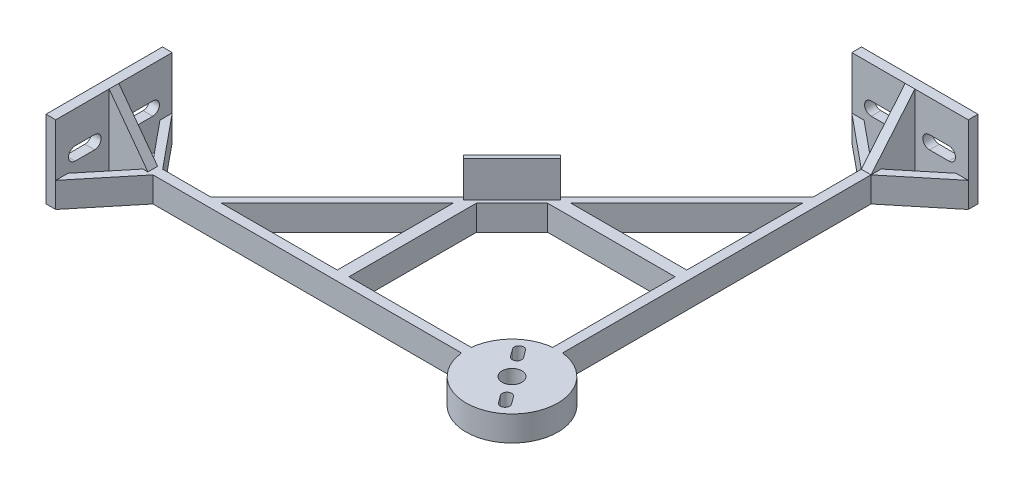
SolidWorks part; units mm, degrees
material "ABS"
ref_plane "Front Plane" through (0, 0, 0) normal (0, 0, 1) x (1, 0, 0)
ref_plane "Top Plane" through (0, 0, 0) normal (0, 1, 0) x (1, 0, 0)
ref_plane "Right Plane" through (0, 0, 0) normal (1, 0, 0) x (0, 0, -1)
sketch "Sketch1" plane through (0, 0, 0) normal (0, 1, 0) x (1, 0, 0)
  line L0 (-1.5875, 14.9158) -> (-1.5875, 130.175)
  line L1 (1.5875, 130.175) -> (1.5875, 14.9158)
  line L2 (-1.5875, 130.175) -> (1.5875, 130.175)
  line L4 (-14.9158, -1.5875) -> (-130.175, -1.5875)
  line L5 (-130.175, -1.5875) -> (-130.175, 1.5875)
  line L8 (-130.175, 1.5875) -> (-14.9158, 1.5875)
  line L9 (0, 0) -> (-130.175, 0) construction
  line L11 (0, 0) -> (0, 146.05) construction
  circle A0 centre (0, 0) radius 15
  point P19 (0, 0)
  point P21 (0, 0)
  dimension "D1" = 30
  dimension "D2" = 3.175
  dimension "D4" = 1.5875
  dimension "D3" = 2
  dimension "D5" = 130.175
extrude "Boss-Extrude2" add sketch "Sketch1" along normal blind 8.255 contours A0
extrude "Boss-Extrude3" add sketch "Sketch1<6>" along normal blind 8.255 contours L4 A0 | A0 | A0 region at (0, 0, -72.5735) region at (-72.5735, 0, 0)
sketch "Sketch1<6>" plane through (0, 0, 0) normal (0, 1, 0) x (1, 0, 0) same geometry as "Sketch1"
sketch "Sketch5" plane through (0, 8.255, 0) normal (0, 1, 0) x (1, 0, 0)
  line L0 (0, 0) -> (130.175, 0) construction
  line L1 (0, 0) -> (0, -22.3627) construction
  line L2 (-6.4967, 8.7797) -> (0, 0) construction
  line L3 (-4.6836, 6.3296) -> (-6.4967, 8.7797) construction
  line L4 (-5.9087, 5.4231) -> (-7.7217, 7.8732)
  line L5 (-3.4586, 7.2361) -> (-5.2716, 9.6862)
  line L6 (0, 0) -> (1.0099, 0.7473) construction
  line L7 (4.6836, -6.3296) -> (6.4967, -8.7797) construction
  line L8 (3.4586, -7.2361) -> (5.2716, -9.6862)
  line L9 (5.9087, -5.4231) -> (7.7217, -7.8732)
  line L10 (-1.5875, 130.175) -> (1.5875, 130.175) construction
  arc A0 (3.4586, -7.2361) -> (5.9087, -5.4231) centre (4.6836, -6.3296) cw
  arc A1 (-5.9087, 5.4231) -> (-3.4586, 7.2361) centre (-4.6836, 6.3296) ccw
  arc A2 (-5.2716, 9.6862) -> (-7.7217, 7.8732) centre (-6.4967, 8.7797) ccw
  arc A3 (7.7217, -7.8732) -> (5.2716, -9.6862) centre (6.4967, -8.7797) cw
  circle A6 centre (0, 0) radius 3.25
  point P8 (-5.5901, 7.5546)
  point P17 (5.5901, -7.5546)
  point P18 (0, 0)
  dimension "D3" = 3.048
  dimension "D1" = 7.874
  dimension "D2" = 3.048
  dimension "D4" = 53.5
extrude "Cut-Extrude3" cut sketch "Sketch5" against normal blind 63.5
ref_axis "Axis1" through (0, 0, 0) along (0, 1, 0)
ref_plane "Plane1" through (0, 0, 0) normal (0, 0, 1) x (1, 0, 0)
ref_plane "Plane2" through (0, 0, 0) normal (1, 0, 0) x (0, 0, -1)
sketch "Sketch7" plane through (0, 0, 0) normal (1, 0, 0) x (0, 0, -1)
  line L1 (130.175, 0) -> (133.35, 0)
  line L2 (130.175, 0) -> (130.175, 25.4)
  line L3 (130.175, 25.4) -> (133.35, 25.4)
  line L4 (133.35, 0) -> (133.35, 25.4)
  dimension "D1" = 3.175
  dimension "D2" = 25.4
extrude "Boss-Extrude5" add sketch "Sketch7" along normal blind 19.05 and the other way blind 19.05
sketch "Sketch8" plane through (-19.05, 0, 0) normal (-1, 0, 0) x (0, 0, 1)
  line L1 (-133.35, 0) -> (-130.175, 0)
  line L2 (-133.35, 0) -> (-133.35, 25.4)
  line L3 (-133.35, 25.4) -> (-130.175, 25.4)
  line L4 (-130.175, 0) -> (-130.175, 25.4)
sketch "Sketch12" plane through (0, 0, -133.35) normal (0, 0, -1) x (-1, 0, 0)
  line L0 (-19.05, 12.7) -> (19.05, 12.7) construction
  line L1 (-19.05, 0) -> (-19.05, 25.4) construction
  line L2 (19.05, 0) -> (19.05, 25.4) construction
  line L3 (-6.35, 12.7) -> (-12.7, 12.7) construction
  line L4 (-6.35, 10.541) -> (-12.7, 10.541)
  line L5 (-6.35, 14.859) -> (-12.7, 14.859)
  line L6 (6.35, 12.7) -> (12.7, 12.7) construction
  line L7 (6.35, 14.859) -> (12.7, 14.859)
  line L8 (6.35, 10.541) -> (12.7, 10.541)
  line L9 (0, 12.7) -> (0, 25.4) construction
  line L10 (19.05, 25.4) -> (-19.05, 25.4) construction
  arc A0 (-6.35, 10.541) -> (-6.35, 14.859) centre (-6.35, 12.7) ccw
  arc A1 (-12.7, 14.859) -> (-12.7, 10.541) centre (-12.7, 12.7) ccw
  arc A2 (6.35, 14.859) -> (6.35, 10.541) centre (6.35, 12.7) ccw
  arc A3 (12.7, 10.541) -> (12.7, 14.859) centre (12.7, 12.7) ccw
  point P8 (-9.525, 12.7)
  point P13 (9.525, 12.7)
  dimension "D1" = 6.35
  dimension "D2" = 4.318
  dimension "D3" = 4.318
  dimension "D4" = 6.35
  dimension "D5" = 9.525
  dimension "D6" = 9.525
extrude "Cut-Extrude6" cut sketch "Sketch12" against normal through all
pattern_circular "CirPattern2" count 2 every 90 about axis through (0, 0, 0) along (0, 1, 0) of "Boss-Extrude5"
pattern_circular "CirPattern3" count 2 every 90 about axis through (0, 0, 0) along (0, 1, 0) of "Cut-Extrude6"
sketch "Sketch13" plane through (0, 0, 0) normal (0, -1, 0) x (1, 0, 0)
  line L0 (-96.6289, -1.5875) -> (-1.5875, -96.6289)
  line L1 (-130.175, -1.5875) -> (-14.9158, -1.5875) construction
  line L2 (-1.5875, -14.9158) -> (-1.5875, -130.175) construction
  line L3 (-100.2211, -1.5875) -> (-1.5875, -100.2211)
  line L4 (-96.6289, -1.5875) -> (-100.2211, -1.5875)
  line L5 (-1.5875, -100.2211) -> (-1.5875, -96.6289)
  line L6 (-19.05, -130.175) -> (-1.5875, -130.175) construction
  line L7 (-130.175, -1.5875) -> (-130.175, -19.05) construction
  line L8 (-19.05, -130.175) -> (-1.5875, -115.8315)
  line L9 (-1.5875, -115.8315) -> (-1.5875, -119.1185)
  line L10 (-1.5875, -119.1185) -> (-15.0482, -130.175)
  line L11 (-15.0482, -130.175) -> (-19.05, -130.175)
  line L12 (19.05, -130.175) -> (1.5875, -115.8315)
  line L13 (1.5875, -130.175) -> (1.5875, -14.9158) construction
  line L14 (1.5875, -115.8315) -> (1.5875, -119.1185)
  line L15 (1.5875, -119.1185) -> (15.0482, -130.175)
  line L16 (1.5875, -130.175) -> (19.05, -130.175) construction
  line L17 (15.0482, -130.175) -> (19.05, -130.175)
  line L18 (-119.1185, 1.5875) -> (-130.175, 15.0482)
  line L19 (-130.175, 19.05) -> (-115.8315, 1.5875)
  line L20 (-130.175, 15.0482) -> (-130.175, 19.05)
  line L21 (-119.1185, -1.5875) -> (-130.175, -15.0482)
  line L22 (-130.175, -19.05) -> (-115.8315, -1.5875)
  line L23 (-115.8315, -1.5875) -> (-119.1185, -1.5875)
  line L24 (-115.8315, 1.5875) -> (-119.1185, 1.5875)
  line L25 (-130.175, -15.0482) -> (-130.175, -19.05)
  point P8 (-1.5875, -72.5454)
  point P9 (-1.5875, -98.425)
  point P12 (-98.425, -1.5875)
  point P25 (-1.5875, -117.475)
  point P30 (1.5875, -117.475)
  point P42 (0, 0)
  dimension "D1" = 31.75
  dimension "D2" = 31.75
  dimension "D3" = 2.54
  dimension "D4" = 2.54
  dimension "D5" = 2.54
  dimension "D6" = 12.7
  dimension "D7" = 2
extrude "Boss-Extrude6" add sketch "Sketch13" against normal up to surface (8.255 mm away) up to face at (0, 8.255, 3.25)
sketch "Sketch14" plane through (0, 0, 0) normal (0, 0, 1) x (1, 0, 0)
  line L0 (-130.175, 25.4) -> (-117.475, 8.255)
  line L1 (-14.9158, 8.255) -> (-115.8315, 8.255) construction
  line L2 (-117.475, 8.255) -> (-130.175, 8.255)
  line L3 (-130.175, 8.255) -> (-130.175, 25.4)
  dimension "D1" = 12.7
extrude "Boss-Extrude7" add sketch "Sketch14" along normal up to surface and the other way up to surface up to face at (-124.6467, 4.1275, 1.5875) other way up to face at (-124.6467, 4.1275, -1.5875)
sketch "Sketch15" plane through (0, 0, 0) normal (1, 0, 0) x (0, 0, -1)
  line L0 (130.175, 25.4) -> (115.8315, 8.255)
  line L1 (115.8315, 8.255) -> (115.8315, 0) construction
  line L2 (130.175, 8.255) -> (115.8315, 8.255) construction
  line L3 (115.8315, 8.255) -> (130.175, 8.255)
  line L4 (130.175, 8.255) -> (130.175, 25.4)
extrude "Boss-Extrude8" add sketch "Sketch15" along normal up to surface and the other way up to surface up to face at (1.5875, 4.1275, -65.3736) other way up to face at (-1.5875, 4.1275, -108.0263)
sketch "Sketch19" plane through (-1.5875, 0, 0) normal (-1, 0, 0) x (0, 0, 1)
  line L0 (-58.7308, 8.255) -> (-58.7308, 0)
  line L1 (-14.9158, 8.255) -> (-96.6289, 8.255) construction
  line L2 (-14.9158, 0) -> (-96.6289, 0) construction
  line L3 (-54.9208, 8.255) -> (-54.9208, 0)
  line L4 (-58.7308, 8.255) -> (-54.9208, 8.255)
  line L5 (-54.9208, 0) -> (-58.7308, 0)
  line L6 (-14.9158, 8.255) -> (-14.9158, 0) construction
  point P10 (-56.8258, 0)
  point P13 (-46.6233, 31.1523)
  dimension "D1" = 41.91
  dimension "D2" = 3.81
extrude "Boss-Extrude9" add sketch "Sketch19" along normal up to next
sketch "Sketch20" plane through (0, 0, -1.5875) normal (0, 0, -1) x (-1, 0, 0)
  line L0 (54.9208, 0) -> (54.9208, 8.255)
  line L1 (96.6289, 0) -> (14.9158, 0) construction
  line L2 (96.6289, 8.255) -> (14.9158, 8.255) construction
  line L3 (54.9208, 8.255) -> (58.7308, 8.255)
  line L4 (58.7308, 8.255) -> (58.7308, 0)
  line L5 (54.9208, 0) -> (58.7308, 0)
  line L6 (14.9158, 8.255) -> (14.9158, 0) construction
  point P6 (56.8258, 0)
  dimension "D1" = 41.91
  dimension "D2" = 3.81
extrude "Boss-Extrude10" add sketch "Sketch20" along normal up to next
ref_plane "Plane3" through (-50.0062, 0, -50.0063) normal (-0.7071, 0, -0.7071) x (-0.7071, 0, 0.7071)
sketch "Sketch21" plane through (-50.0062, 0, -50.0063) normal (-0.7071, 0, -0.7071) x (-0.7071, 0, 0.7071)
  line L0 (-11.176, 0) -> (11.176, 0)
  line L1 (69.7445, 0) -> (-69.7445, 0) construction
  line L2 (11.176, 0) -> (11.176, 20.066)
  line L3 (-11.176, 20.066) -> (11.176, 20.066)
  line L4 (0, 20.066) -> (0, 0) construction
  line L5 (-11.176, 0) -> (-11.176, 20.066)
  point P8 (0, 0)
  dimension "D1" = 11.176
extrude "Boss-Extrude11" add sketch "Sketch21" along normal up to surface (1.27 mm away) up to face at (-50.9043, 4.1275, -50.9043)
